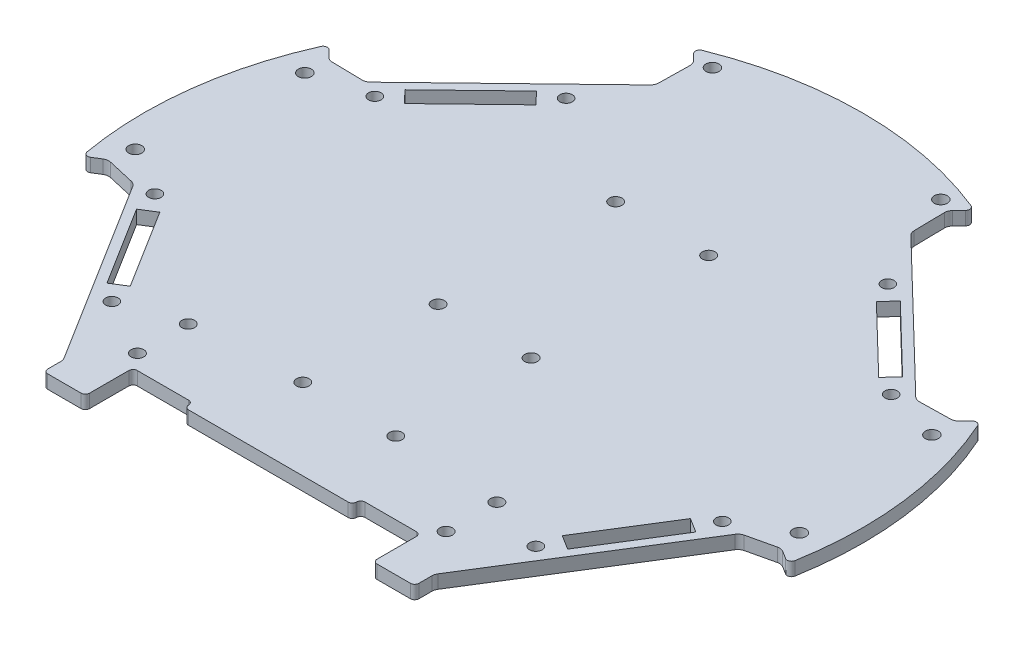
SolidWorks part; units mm, degrees
material "6061 Alloy"
ref_plane "Front Plane" through (0, 0, 0) normal (0, 0, 1) x (1, 0, 0)
ref_plane "Top Plane" through (0, 0, 0) normal (0, 1, 0) x (1, 0, 0)
ref_plane "Right Plane" through (0, 0, 0) normal (1, 0, 0) x (0, 0, -1)
sketch "Sketch1" plane through (0, 0, 0) normal (0, 1, 0) x (1, 0, 0)
  line L0 (0, 0) -> (0, -55.55) construction
  line L1 (-83.4462, -16.178) -> (-71.2857, -8.5793) construction
  line L6 (0, 0) -> (-59.046, 61.1439) construction
  line L7 (0, 0) -> (-72.0841, -45.0431) construction
  line L8 (-33.174, 78.2591) -> (-23.2129, 67.9442) construction
  line L9 (-72.0841, -45.0431) -> (-70.388, -43.9833) construction
  line L10 (-70.388, -43.9833) -> (-84.9608, -20.662) construction
  line L11 (-84.9608, -20.662) -> (-72.2401, -12.7132) construction
  line L12 (-72.2401, -12.7132) -> (-43.0945, -59.3558) construction
  line L13 (-43.0945, -59.3558) -> (-55.8152, -67.3046) construction
  line L14 (-55.8152, -67.3046) -> (-70.388, -43.9833) construction
  line L21 (-59.046, 61.1439) -> (-57.6566, 59.7052)
  line L22 (-77.4385, 40.6021) -> (-37.8748, 78.8083) construction
  line L23 (-73.9694, 32.6911) -> (-77.0537, 35.885)
  line L24 (-37.8748, 78.8083) -> (-27.4549, 68.0182) construction
  line L25 (-27.4549, 68.0182) -> (-67.0186, 29.812) construction
  line L26 (-67.0186, 29.812) -> (-77.4385, 40.6021) construction
  line L27 (-43.0945, -64.8266) -> (-34, -64.8266)
  line L33 (-86.5505, -18.1178) -> (-71.2857, -8.5793) construction
  line L34 (0, 0) -> (0, 50000) construction
  line L35 (0, 0) -> (-50000, 0) construction
  line L36 (-64.3366, -55.55) -> (-19.7189, -55.55) construction
  line L38 (-67.0927, 25.57) -> (-79.5965, 38.5181) construction
  line L39 (-54.9774, -64.8266) -> (0, -64.8266) construction
  line L40 (-35.7168, 80.8923) -> (-23.2129, 67.9442) construction
  line L41 (-38.9606, -60.3102) -> (-54.2255, -69.8488) construction
  line L42 (-34, -55.55) -> (-19.7189, -55.55) construction
  line L43 (-43.0945, -64.8266) -> (-43.0945, -58.4123) construction
  line L45 (73.9694, 32.6911) -> (77.0537, 35.885)
  line L46 (-71.2857, -8.5793) -> (-38.9606, -60.3102) construction
  line L47 (83.4462, -16.178) -> (79.6809, -13.8252)
  line L48 (69.4846, -16.1792) -> (43.8945, -57.132)
  line L50 (43.0945, -64.8266) -> (34, -64.8266)
  line L51 (34, -55.55) -> (34, -64.8266)
  line L52 (0, 0) -> (72.0841, -45.0431) construction
  line L53 (0, 0) -> (59.046, 61.1439) construction
  line L54 (-30.0897, 75.0653) -> (-30.2847, 63.8954)
  line L55 (-62.7996, 32.4961) -> (-30.2847, 63.8954)
  line L56 (-30.0897, 75.0653) -> (-33.174, 78.2591)
  line L57 (73.9694, 32.6911) -> (77.0537, 35.885)
  line L58 (30.0897, 75.0653) -> (33.174, 78.2591)
  line L59 (-34, -55.55) -> (-34, -53.55)
  line L60 (62.7996, 32.4961) -> (30.2847, 63.8954)
  line L61 (-73.9694, 32.6911) -> (-62.7996, 32.4961)
  line L62 (-77.0537, 35.885) -> (-67.0927, 25.57) construction
  line L63 (-83.4462, -16.178) -> (-79.6809, -13.8252)
  line L64 (-79.6809, -13.8252) -> (-69.4846, -16.1792)
  line L65 (-69.4846, -16.1792) -> (-43.8945, -57.132)
  line L66 (-27.4549, 68.0182) -> (-23.2129, 67.9442) construction
  line L67 (-72.2401, -12.7132) -> (-71.2857, -8.5793) construction
  line L68 (30.0897, 75.0653) -> (30.2847, 63.8954)
  line L69 (73.9694, 32.6911) -> (62.7996, 32.4961)
  line L70 (-34, -55.55) -> (-34, -64.8266)
  line L71 (79.6809, -13.8252) -> (69.4846, -16.1792)
  line L72 (-34, -53.55) -> (-20, -53.55)
  line L73 (-20, -53.55) -> (-19.7189, -55.55)
  line L74 (-19.7189, -55.55) -> (19.7189, -55.55)
  line L75 (20, -53.55) -> (19.7189, -55.55)
  line L76 (34, -53.55) -> (20, -53.55)
  line L77 (34, -55.55) -> (34, -53.55)
  line L78 (-43.0945, -64.8266) -> (-43.8945, -64.8266)
  line L79 (-19.7189, -55.55) -> (0, -55.55) construction
  line L80 (-19.7189, -55.55) -> (34, -55.55) construction
  line L81 (-43.8945, -64.8266) -> (-43.8945, -57.132)
  line L82 (-43.0945, -58.4123) -> (-43.8945, -57.132) construction
  line L83 (43.8945, -64.8266) -> (43.8945, -57.132)
  line L84 (43.0945, -64.8266) -> (43.8945, -64.8266)
  line L97 (-23.2129, 67.9442) -> (-67.0927, 25.57) construction
  circle A0 centre (0, 0) radius 85 construction
  circle A1 centre (0, 0) radius 90 construction
  arc A51 (-77.0537, 35.885) -> (-83.4462, -16.178) centre (0, 0) ccw
  arc A52 (77.0537, 35.885) -> (83.4462, -16.178) centre (0, 0) cw
  arc A54 (-33.174, 78.2591) -> (33.174, 78.2591) centre (0, 0) cw
  point P29 (-31.6318, 76.6622)
  point P33 (-47.2368, 48.9151)
  point P34 (31.6318, 76.6622)
  point P35 (-57.6673, -36.0345)
  point P85 (-57.6566, 59.7052)
  dimension "D2" = 58
  dimension "D10" = 82
  dimension "D12" = 170
  dimension "D14" = 34
  dimension "D13" = 2
  dimension "D15" = 3
  dimension "D3" = 180
  dimension "D4" = 64.8266
  dimension "D5" = 44
  dimension "D6" = 15
  dimension "D7" = 55
  dimension "D8" = 55.55
  dimension "D9" = 2
  dimension "D11" = 2
  dimension "D16" = 7
  dimension "D17" = 7
  dimension "D18" = 0.5
  dimension "D19" = 1
  dimension "D20" = 14
  dimension "D21" = 0.8
extrude "Boss-Extrude4" add sketch "Sketch1" along normal mid plane 3.175 contours A0 L70 region at (0, 0, -7.394)
ref_point "Rear_Axle_Center (L)"
ref_axis "Rear_Axle_Proj (L)" through (46.5421, 0, -48.1958) along (0, 1, 0)
ref_point "Front_Axle_Center (L)"
ref_axis "Front_Axle_Proj (L)" through (57.2432, 0, 35.7696) along (0, 1, 0)
ref_point "Front_Axle_Center (R)"
ref_axis "Front_Axle_Proj (R)" through (-57.2432, 0, 35.7696) along (0, 1, 0)
ref_point "Read_Axle_Center (R)"
ref_axis "Rear_Axle_Proj (R)" through (-46.5421, 0, -48.1958) along (0, 1, 0)
sketch "Sketch17" plane through (0, 1.5875, 0) normal (0, 1, 0) x (1, 0, 0)
  line L0 (0, -50.55) -> (0, -55.55) construction
  line L1 (-19.7189, -55.55) -> (19.7189, -55.55) construction
  circle A0 centre (0, -50.55) radius 8.5
  dimension "D1" = 17
  dimension "D2" = 5
extrude "Boss-Extrude5" [suppressed] add sketch "Sketch17" against normal up to surface (3.175 mm away)
ref_plane "Plane1" through (0, 0, 10) normal (0, 0, 1) x (1, 0, 0)
hole_wizard "M3 Clearance Hole3" positions "Sketch18" profile "Sketch19" hole size "M3" standard "ANSI Metric" end condition through all
sketch "Sketch18" plane through (0, -1.5875, 0) normal (0, -1, 0) x (-1, 0, 0)
  line L0 (-36.5, -50) -> (-36.5, -38) construction
  line L3 (0, 0) -> (0, -38) construction
  line L4 (36.5, -50) -> (36.5, -38) construction
  line L6 (0, -38) -> (36.5, -38) construction
  line L8 (0, -38) -> (-36.5, -38) construction
  line L9 (-36.5, -44) -> (36.5, -44) construction
  line L10 (0, -44) -> (0, 0) construction
  point P1 (36.5, -50)
  point P3 (36.5, -38)
  point P5 (-36.5, -50)
  point P33 (-36.5, -38)
  dimension "D1" = 12
  dimension "D2" = 73
  dimension "D4" = 38
sketch "Sketch19" plane through (-36.5, -1.5875, 50) normal (1, 0, 0) x (0, 0, -1)
  line L0 (0, 0) -> (0, 3.175)
  line L1 (0, 3.175) -> (1.5, 3.175)
  line L2 (1.5, 3.175) -> (1.5, 0)
  line L5 (1.5, 0) -> (0, 0)
  line L11 (0, -6.35) -> (0, 107.95) construction
  dimension "Thru Hole Dia." = 3
  dimension "Thru Hole Depth" = 3.175
hole_wizard "M3 Clearance Hole1" positions "Sketch11" profile "Sketch12" hole size "M3" standard "ANSI Metric" end condition through all
sketch "Sketch11" plane through (0, 1.5875, 0) normal (0, 1, 0) x (1, 0, 0)
  line L0 (83.4462, -16.178) -> (79.6809, -13.8252) construction
  line L2 (73.9694, 32.6911) -> (77.0537, 35.885) construction
  line L4 (-73.9694, 32.6911) -> (-77.0537, 35.885) construction
  line L6 (0, 0) -> (0, -50000) construction
  line L7 (78.4111, 9.6277) -> (84.3664, 10.3589) construction
  line L10 (74.155, 27.2403) -> (78.5423, -8.4914) construction
  line L12 (78.4111, 9.6277) -> (76.3487, 9.3744) construction
  arc A7 (77.964, -12.7523) -> (72.563, 31.2347) centre (0, 0) ccw construction
  arc A13 (-77.964, -12.7523) -> (-72.563, 31.2347) centre (0, 0) cw construction
  arc A17 (83.4462, -16.178) -> (77.0537, 35.885) centre (0, 0) ccw construction
  point P34 (78.5423, -8.4914)
  point P66 (74.155, 27.2403)
  point P70 (-74.155, 27.2403)
  point P71 (-78.5423, -8.4914)
  dimension "D1" = 6
  dimension "D2" = 36
sketch "Sketch12" plane through (-78.5423, 1.5875, 8.4914) normal (1, 0, 0) x (0, 0, 1)
  line L0 (0, 0) -> (0, 3.175)
  line L1 (0, 3.175) -> (1.55, 3.175)
  line L2 (1.55, 3.175) -> (1.55, 0)
  line L5 (1.55, 0) -> (0, 0)
  line L11 (0, -6.35) -> (0, 107.95) construction
  dimension "Thru Hole Dia." = 3.1
  dimension "Thru Hole Depth" = 3.175
hole_wizard "M3 Clearance Hole4" positions "Sketch9" profile "Sketch10" hole size "M3" standard "ANSI Metric" end condition through all
sketch "Sketch9" plane through (0, -1.5875, 0) normal (0, -1, 0) x (-1, 0, 0)
  line L0 (0, 0) -> (0, 63.4318) construction
  line L1 (-38.0437, 52.9272) -> (38.0437, 52.9272) construction
  line L3 (61.0625, 30.6981) -> (-61.0625, 30.6981) construction
  line L4 (-67.0993, -15.2789) -> (67.0993, -15.2789) construction
  line L5 (50.1419, -42.4164) -> (-50.1419, -42.4164) construction
  line L6 (-61.0625, 30.6981) -> (-38.0437, 52.9272) construction
  line L7 (38.0437, 52.9272) -> (61.0625, 30.6981) construction
  line L8 (67.0993, -15.2789) -> (50.1419, -42.4164) construction
  line L9 (-50.1419, -42.4164) -> (-67.0993, -15.2789) construction
  line L10 (0, 0) -> (-44.8055, 46.3974) construction
  line L11 (0, 0) -> (44.8055, 46.3974) construction
  line L12 (0, 0) -> (-96.9468, 0) construction
  line L14 (-55.1231, -34.4448) -> (0, 0) construction
  line L15 (0, 0) -> (55.1231, -34.4448) construction
  line L18 (-69.4846, -16.1792) -> (-43.8945, -57.132) construction
  line L19 (-62.7996, 32.4961) -> (-30.2847, 63.8954) construction
  point P0 (-67.0993, -15.2789)
  point P2 (-50.1419, -42.4164)
  point P9 (-61.0625, 30.6981)
  point P11 (-38.0437, 52.9272)
  point P30 (50.1419, -42.4164)
  point P31 (67.0993, -15.2789)
  point P32 (38.0437, 52.9272)
  point P33 (61.0625, 30.6981)
  dimension "D9" = 46
  dimension "D10" = 46
  dimension "D11" = 32
  dimension "D12" = 32
  dimension "D7" = 58
  dimension "D5" = 32
  dimension "D6" = 2.5
  dimension "D8" = 9.4
  dimension "D2" = 44
  dimension "D3" = 32
  dimension "D4" = 2.5
  dimension "D13" = 9.4
sketch "Sketch10" plane through (67.0993, -1.5875, 15.2789) normal (1, 0, 0) x (0, 0, -1)
  line L0 (0, 0) -> (0, 3.175)
  line L1 (0, 3.175) -> (1.475, 3.175)
  line L2 (1.475, 3.175) -> (1.475, 0)
  line L5 (1.475, 0) -> (0, 0)
  line L11 (0, -6.35) -> (0, 107.95) construction
  dimension "Thru Hole Dia." = 2.95
  dimension "Thru Hole Depth" = 3.175
hole_wizard "M3 Clearance Hole2" positions "Sketch13" profile "Sketch14" hole size "M3" standard "ANSI Metric" end condition through all
sketch "Sketch13" plane through (0, 1.5875, 0) normal (0, 1, 0) x (1, 0, 0)
  line L0 (0, 0) -> (0, 85) construction
  line L2 (-24, 47) -> (-24, 81) construction
  line L3 (-24, 47) -> (24, 47) construction
  line L4 (-24, 81) -> (24, 81) construction
  line L5 (24, 47) -> (24, 81) construction
  line L6 (-24, 47) -> (24, 81) construction
  line L7 (-24, 81) -> (24, 47) construction
  line L8 (-38.0437, 52.9272) -> (-61.0625, 30.6981) construction
  line L10 (-36.307, 51.1289) -> (-59.3259, 28.8998) construction
  line L11 (-16.3488, 39.8187) -> (-31.6313, 55.6441) construction
  line L12 (-16.3488, 39.8187) -> (-48.7191, 8.559) construction
  line L13 (-31.6313, 55.6441) -> (-64.0016, 24.3845) construction
  line L14 (-48.7191, 8.559) -> (-64.0016, 24.3845) construction
  line L15 (-16.3488, 39.8187) -> (-64.0016, 24.3845) construction
  line L16 (-31.6313, 55.6441) -> (-48.7191, 8.559) construction
  line L17 (-49.5531, 41.8127) -> (-40.1752, 32.1016) construction
  line L18 (-27, 76.4978) -> (-27, 80.5978) construction
  arc A0 (33.174, 78.2591) -> (-33.174, 78.2591) centre (0, 0) ccw construction
  circle A1 centre (-16.2162, 44) radius 3 construction
  circle A2 centre (-27, 76.4978) radius 3 construction
  point P65 (0, 64)
  point P181 (-27, 76.4978)
  point P184 (27, 76.4978)
  dimension "D7" = 6
  dimension "D1" = 48
  dimension "D2" = 34
  dimension "D3" = 4
  dimension "D5" = 45
  dimension "D6" = 22
  dimension "D8" = 4.1
  dimension "D4" = 2.5
sketch "Sketch14" plane through (27, 1.5875, -76.4978) normal (1, 0, 0) x (0, 0, 1)
  line L0 (0, 0) -> (0, 3.175)
  line L1 (0, 3.175) -> (1.55, 3.175)
  line L2 (1.55, 3.175) -> (1.55, 0)
  line L5 (1.55, 0) -> (0, 0)
  line L11 (0, -6.35) -> (0, 107.95) construction
  dimension "Thru Hole Dia." = 3.1
  dimension "Thru Hole Depth" = 3.175
hole_wizard "M3 Clearance Hole5" positions "Sketch24" profile "Sketch25" hole size "M3" standard "ANSI Metric" end condition through all
sketch "Sketch24" plane through (0, 1.5875, 0) normal (0, 1, 0) x (1, 0, 0)
  line L1 (-11, -4.4) -> (11, -4.4) construction
  line L2 (11, -4.4) -> (11, -36.4) construction
  line L3 (11, -36.4) -> (-11, -36.4) construction
  line L4 (-11, -36.4) -> (-11, -4.4) construction
  line L7 (-11, 37.6) -> (11, 37.6) construction
  line L8 (0, -4.4) -> (0, 0) construction
  line L9 (0, 0) -> (0, 37.6) construction
  point P8 (-11, -4.4)
  point P10 (11, -4.4)
  point P12 (11, -36.4)
  point P14 (-11, -36.4)
  point P42 (-11, 37.6)
  point P45 (11, 37.6)
  dimension "D1" = 22
  dimension "D2" = 32
  dimension "D3" = 4.4
  dimension "D4" = 42
sketch "Sketch25" plane through (-11, 1.5875, 4.4) normal (1, 0, 0) x (0, 0, 1)
  line L0 (0, 0) -> (0, 3.175)
  line L1 (0, 3.175) -> (1.5, 3.175)
  line L2 (1.5, 3.175) -> (1.5, 0)
  line L5 (1.5, 0) -> (0, 0)
  line L11 (0, -6.35) -> (0, 107.95) construction
  dimension "Thru Hole Dia." = 3
  dimension "Thru Hole Depth" = 3.175
sketch "Sketch20" plane through (0, 1.5875, 0) normal (0, 1, 0) x (1, 0, 0)
  line L0 (-16.1485, 44) -> (-16.1485, 39) construction
  line L1 (-14.6485, 44) -> (-14.6485, 39)
  line L2 (-17.6485, 44) -> (-17.6485, 39)
  line L3 (0, 0) -> (0, 85) construction
  line L5 (16.1485, 44) -> (16.1485, 39) construction
  line L6 (14.6485, 44) -> (14.6485, 39)
  line L7 (17.6485, 44) -> (17.6485, 39)
  arc A0 (-14.6485, 44) -> (-17.6485, 44) centre (-16.1485, 44) ccw
  arc A1 (-17.6485, 39) -> (-14.6485, 39) centre (-16.1485, 39) ccw
  arc A5 (33.174, 78.2591) -> (-33.174, 78.2591) centre (0, 0) ccw construction
  arc A7 (14.6485, 44) -> (17.6485, 44) centre (16.1485, 44) cw
  arc A8 (17.6485, 39) -> (14.6485, 39) centre (16.1485, 39) cw
  point P2 (-16.1485, 41.5)
  point P16 (16.1485, 41.5)
  dimension "D1" = 44
  dimension "D2" = 3
  dimension "D3" = 5
  dimension "D4" = 16.1485
extrude "Cut-Extrude1" [suppressed] cut sketch "Sketch20" against normal through all
sketch "Sketch22" plane through (0, 1.5875, 0) normal (0, 1, 0) x (1, 0, 0)
  line L0 (-56.6896, -36.6556) -> (-58.0464, -37.5035) construction
  line L1 (-69.4846, -16.1792) -> (-43.8945, -57.132) construction
  line L3 (30.2452, 66.1578) -> (65.062, 32.5356)
  line L4 (71.6894, -15.6702) -> (43.8945, -60.1514)
  line L5 (-19.7189, -55.55) -> (19.7189, -55.55) construction
  line L6 (-43.8945, -64.8266) -> (-43.8945, -57.132) construction
  line L28 (-30.2452, 66.1578) -> (-65.062, 32.5356)
  line L29 (-71.6894, -15.6702) -> (-43.8945, -60.1514)
  line L30 (-79.6809, -13.8252) -> (-69.4846, -16.1792) construction
  line L31 (0, 85) -> (0, -55.55) construction
  line L32 (-46.5421, 48.1958) -> (-47.6536, 49.3467) construction
  line L37 (-20, -53.55) -> (-19.7189, -55.55)
  line L38 (-20, -53.55) -> (-19.7189, -55.55)
  line L40 (-43.8945, -57.132) -> (-43.8945, -64.8266)
  line L41 (-43.8945, -57.132) -> (-43.8945, -64.8266)
  line L43 (43.8945, -64.8266) -> (43.8945, -57.132)
  line L44 (43.8945, -64.8266) -> (43.8945, -57.132)
  line L56 (-19.7189, -55.55) -> (19.7189, -55.55)
  line L58 (19.7189, -55.55) -> (20, -53.55)
  line L59 (20, -53.55) -> (34, -53.55)
  line L60 (34, -53.55) -> (34, -64.8266)
  line L61 (34, -64.8266) -> (43.8945, -64.8266)
  line L63 (43.8945, -57.132) -> (69.4846, -16.1792)
  line L64 (69.4846, -16.1792) -> (79.6809, -13.8252)
  line L65 (79.6809, -13.8252) -> (83.4462, -16.178)
  line L66 (77.0537, 35.885) -> (73.9694, 32.6911)
  line L67 (73.9694, 32.6911) -> (62.7996, 32.4961)
  line L68 (62.7996, 32.4961) -> (30.2847, 63.8954)
  line L69 (30.2847, 63.8954) -> (30.0897, 75.0653)
  line L70 (30.0897, 75.0653) -> (33.174, 78.2591)
  line L71 (-33.174, 78.2591) -> (-30.0897, 75.0653)
  line L72 (-30.0897, 75.0653) -> (-30.2847, 63.8954)
  line L73 (-30.2847, 63.8954) -> (-62.7996, 32.4961)
  line L74 (-62.7996, 32.4961) -> (-73.9694, 32.6911)
  line L75 (-73.9694, 32.6911) -> (-77.0537, 35.885)
  line L76 (-83.4462, -16.178) -> (-79.6809, -13.8252)
  line L77 (-79.6809, -13.8252) -> (-69.4846, -16.1792)
  line L78 (-69.4846, -16.1792) -> (-43.8945, -57.132)
  line L80 (-43.8945, -64.8266) -> (-34, -64.8266)
  line L81 (-34, -64.8266) -> (-34, -53.55)
  line L82 (-34, -53.55) -> (-20, -53.55)
  line L84 (-19.7189, -55.55) -> (19.7189, -55.55)
  line L86 (19.7189, -55.55) -> (20, -53.55)
  line L87 (20, -53.55) -> (34, -53.55)
  line L88 (34, -53.55) -> (34, -64.8266)
  line L89 (34, -64.8266) -> (43.8945, -64.8266)
  line L91 (43.8945, -57.132) -> (69.4846, -16.1792)
  line L92 (69.4846, -16.1792) -> (79.6809, -13.8252)
  line L93 (79.6809, -13.8252) -> (83.4462, -16.178)
  line L94 (77.0537, 35.885) -> (73.9694, 32.6911)
  line L95 (73.9694, 32.6911) -> (62.7996, 32.4961)
  line L96 (62.7996, 32.4961) -> (30.2847, 63.8954)
  line L97 (30.2847, 63.8954) -> (30.0897, 75.0653)
  line L98 (30.0897, 75.0653) -> (33.174, 78.2591)
  line L99 (-33.174, 78.2591) -> (-30.0897, 75.0653)
  line L100 (-30.0897, 75.0653) -> (-30.2847, 63.8954)
  line L101 (-30.2847, 63.8954) -> (-62.7996, 32.4961)
  line L102 (-62.7996, 32.4961) -> (-73.9694, 32.6911)
  line L103 (-73.9694, 32.6911) -> (-77.0537, 35.885)
  line L104 (-83.4462, -16.178) -> (-79.6809, -13.8252)
  line L105 (-79.6809, -13.8252) -> (-69.4846, -16.1792)
  line L106 (-69.4846, -16.1792) -> (-43.8945, -57.132)
  line L108 (-43.8945, -64.8266) -> (-34, -64.8266)
  line L109 (-34, -64.8266) -> (-34, -53.55)
  line L110 (-34, -53.55) -> (-20, -53.55)
  arc A9 (83.4462, -16.178) -> (77.0537, 35.885) centre (0, 0) ccw
  arc A10 (33.174, 78.2591) -> (-33.174, 78.2591) centre (0, 0) ccw
  arc A11 (-77.0537, 35.885) -> (-83.4462, -16.178) centre (0, 0) ccw
  arc A13 (83.4462, -16.178) -> (77.0537, 35.885) centre (0, 0) ccw
  arc A14 (33.174, 78.2591) -> (-33.174, 78.2591) centre (0, 0) ccw
  arc A15 (-77.0537, 35.885) -> (-83.4462, -16.178) centre (0, 0) ccw
  dimension "D2" = 1.6
  dimension "D1" = 0
extrude "Boss-Extrude6" add sketch "Sketch22" against normal up to surface (3.175 mm away) contours L102 L101 L100 L28 | L106 L105 L29 | L92 L91 L4 | L97 L96 L95 L3 region at (47.1042, 1.5875, -48.7778) region at (-47.1042, 1.5875, -48.7778) region at (57.2483, 1.5875, 37.2918) region at (-57.2483, 1.5875, 37.2918) up to face at (-11, -1.5875, 5.9)
fillet "Fillet1" radius 2 14 edges at (-30.0897, 0, -75.0653) (30.0897, 0, -75.0653) (-79.6809, 0, 13.8252) (79.6809, 0, 13.8252) (73.9694, 0, -32.6911) (-73.9694, 0, -32.6911) (65.062, 0, -32.5356) (30.2452, 0, -66.1578) (71.6894, 0, 15.6702) (-71.6894, 0, 15.6702) (-65.062, 0, -32.5356) (-30.2452, 0, -66.1578) (43.8945, 0, 60.1514) (-43.8945, 0, 60.1514)
fillet "Fillet3" radius 1 16 edges at (-77.0537, 0, -35.885) (77.0537, 0, -35.885) (83.4462, 0, 16.178) (34, 0, 64.8266) (-34, 0, 64.8266) (-33.174, 0, -78.2591) (33.174, 0, -78.2591) (-83.4462, 0, 16.178) (20, 0, 53.55) (34, 0, 53.55) (-34, 0, 53.55) (-20, 0, 53.55) (19.7189, 0, 55.55) (-19.7189, 0, 55.55) (-43.8945, 0, 64.8266) (43.8945, 0, 64.8266)
sketch "Sketch23" [suppressed] plane through (0, 3.175, 0) normal (0, 1, 0) x (1, 0, 0)
  circle A0 centre (0, -53.55) radius 4.95
  dimension "D1" = 9.9
extrude "Cut-Extrude2" [suppressed] cut sketch "Sketch23" against normal through all
sketch "Sketch26" [suppressed] plane through (0, 3.175, 0) normal (0, 1, 0) x (1, 0, 0)
  line L0 (0, 0) -> (0, 50) construction
  line L1 (-92.5, 5) -> (92.5, 5)
  line L2 (-92.5, 5) -> (-92.5, 95)
  line L3 (-92.5, 95) -> (92.5, 95)
  line L4 (92.5, 5) -> (92.5, 95)
  line L5 (-92.5, 5) -> (92.5, 95) construction
  line L6 (-92.5, 95) -> (92.5, 5) construction
  point P0 (0, 50)
  dimension "D1" = 90
  dimension "D2" = 185
  dimension "D3" = 5
extrude "Cut-Extrude3" [suppressed] cut sketch "Sketch26" against normal through all
fillet "Fillet4" [suppressed] radius 5
sketch "Sketch27" plane through (0, 1.5875, 0) normal (0, 1, 0) x (1, 0, 0)
  line L0 (71.2504, -16.3728) -> (44.1984, -59.665) construction
  line L1 (45.7962, -45.5968) -> (68.0528, -9.9788) construction
  line L2 (45.7962, -45.5968) -> (49.1884, -47.7165) construction
  line L3 (49.1884, -47.7165) -> (71.445, -12.0985) construction
  line L4 (68.0528, -9.9788) -> (71.445, -12.0985) construction
  line L5 (47.4923, -46.6566) -> (50.1419, -42.4164) construction
  line L6 (51.0954, -37.1163) -> (54.4876, -39.236)
  line L7 (54.4876, -39.236) -> (66.1458, -20.5789)
  line L8 (66.1458, -20.5789) -> (62.7536, -18.4593)
  line L9 (62.7536, -18.4593) -> (51.0954, -37.1163)
  point P6 (50.1419, -42.4164)
  point P7 (67.0993, -15.2789)
  dimension "D1" = 4
  dimension "D2" = 42
  dimension "D3" = 5
  dimension "D4" = 5
  dimension "D5" = 5
extrude "Alignment Cutout - FL" cut sketch "Sketch27" against normal through all
sketch "Sketch28" plane through (0, 1.5875, 0) normal (0, 1, 0) x (1, 0, 0)
  line L1 (-49.1884, -47.7165) -> (-71.445, -12.0985) construction
  line L2 (-49.1884, -47.7165) -> (-45.7962, -45.5968) construction
  line L3 (-45.7962, -45.5968) -> (-68.0528, -9.9788) construction
  line L4 (-71.445, -12.0985) -> (-68.0528, -9.9788) construction
  line L6 (-71.2504, -16.3728) -> (-44.1984, -59.665) construction
  line L7 (-50.1419, -42.4164) -> (-47.4923, -46.6566) construction
  line L8 (-54.4876, -39.236) -> (-51.0954, -37.1163)
  line L9 (-51.0954, -37.1163) -> (-62.7536, -18.4593)
  line L10 (-62.7536, -18.4593) -> (-66.1458, -20.5789)
  line L11 (-66.1458, -20.5789) -> (-54.4876, -39.236)
  point P6 (-67.0993, -15.2789)
  point P7 (-50.1419, -42.4164)
  dimension "D1" = 5
  dimension "D2" = 42
  dimension "D3" = 4
  dimension "D4" = 5
  dimension "D5" = 5
extrude "Alignment Cutout - FR" cut sketch "Sketch28" against normal through all
sketch "Sketch29" plane through (0, 1.5875, 0) normal (0, 1, 0) x (1, 0, 0)
  line L0 (30.8411, 65.5823) -> (64.466, 33.1111) construction
  line L1 (35.8363, 57.8392) -> (66.0486, 28.6635) construction
  line L2 (35.8363, 57.8392) -> (33.0577, 54.9618) construction
  line L3 (33.0577, 54.9618) -> (63.2699, 25.7862) construction
  line L4 (66.0486, 28.6635) -> (63.2699, 25.7862) construction
  line L5 (34.447, 56.4005) -> (38.0437, 52.9272) construction
  line L6 (40.2511, 48.0152) -> (43.0297, 50.8926)
  line L7 (43.0297, 50.8926) -> (58.8552, 35.6101)
  line L8 (58.8552, 35.6101) -> (56.0765, 32.7328)
  line L9 (56.0765, 32.7328) -> (40.2511, 48.0152)
  point P6 (38.0437, 52.9272)
  point P7 (61.0625, 30.6981)
  dimension "D1" = 42
  dimension "D2" = 4
  dimension "D3" = 5
  dimension "D4" = 5
  dimension "D5" = 5
extrude "Alignment Cutout - RL" cut sketch "Sketch29" against normal through all
sketch "Sketch30" plane through (0, 1.5875, 0) normal (0, 1, 0) x (1, 0, 0)
  line L0 (-30.8411, 65.5823) -> (-64.466, 33.1111) construction
  line L1 (-66.0486, 28.6635) -> (-35.8363, 57.8392) construction
  line L2 (-66.0486, 28.6635) -> (-63.2699, 25.7862) construction
  line L3 (-63.2699, 25.7862) -> (-33.0577, 54.9618) construction
  line L4 (-35.8363, 57.8392) -> (-33.0577, 54.9618) construction
  line L5 (-61.0625, 30.6981) -> (-64.6592, 27.2248) construction
  line L6 (-56.0765, 32.7328) -> (-58.8552, 35.6101)
  line L7 (-58.8552, 35.6101) -> (-43.0297, 50.8926)
  line L8 (-43.0297, 50.8926) -> (-40.2511, 48.0152)
  line L9 (-40.2511, 48.0152) -> (-56.0765, 32.7328)
  point P6 (-61.0625, 30.6981)
  point P7 (-38.0437, 52.9272)
  dimension "D1" = 4
  dimension "D2" = 42
  dimension "D3" = 5
  dimension "D4" = 5
  dimension "D5" = 5
extrude "Alignment Cutout - RR" cut sketch "Sketch30" against normal through all
equation "\"D3@Sketch9\"=\"D5@Sketch9\""
equation "\"D4@Sketch9\"=\"D6@Sketch9\""
equation "\"D13@Sketch9\"=\"D8@Sketch9\""
